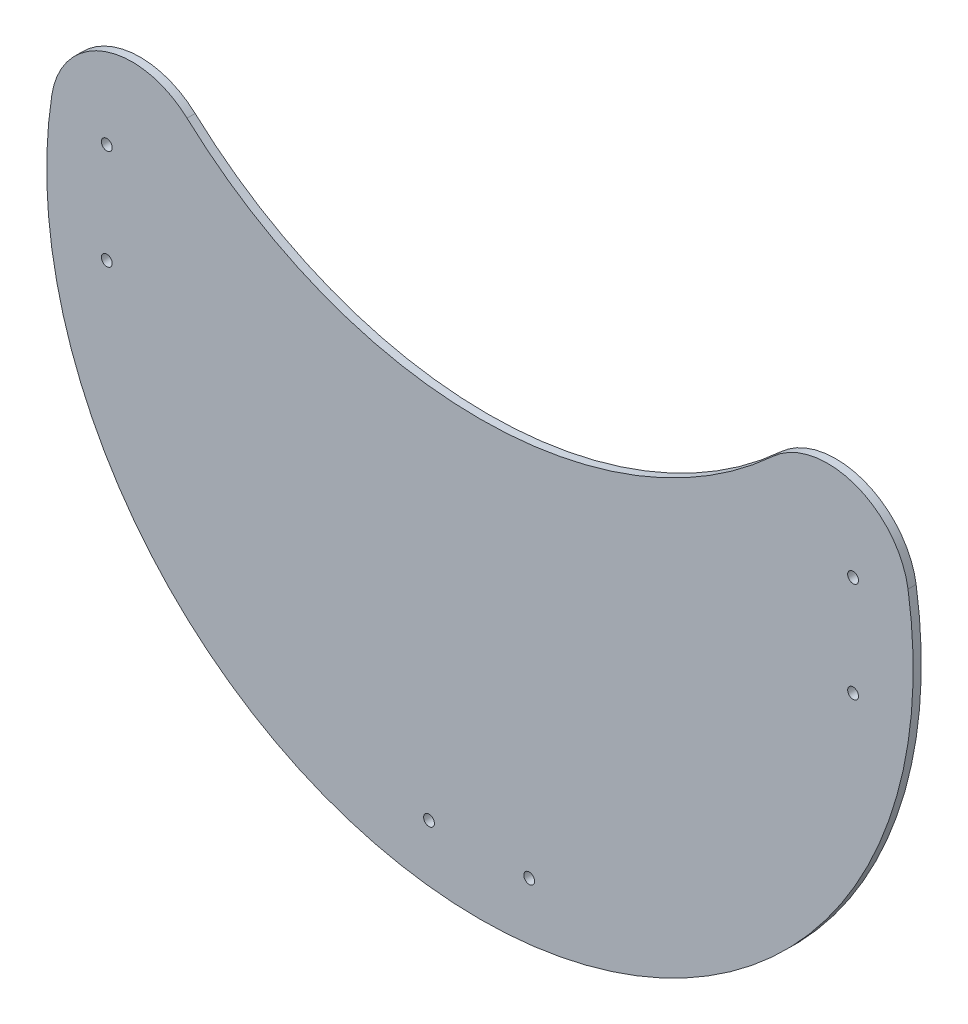
SolidWorks part; units mm, degrees
ref_plane "Front" through (0, 0, 0) normal (0, 0, 1) x (1, 0, 0)
ref_plane "Top" through (0, 0, 0) normal (0, 1, 0) x (1, 0, 0)
ref_plane "Right" through (0, 0, 0) normal (1, 0, 0) x (0, 0, -1)
ref_axis "基准轴1" through (0, -50, 0) along (0, 1, 0)
sketch "草图1" plane through (0, 0, 0) normal (0, 0, 1) x (1, 0, 0)
  circle A6 centre (137.7997, 18.1958) radius 2
  circle A7 centre (137.7997, -18.8042) radius 2
  circle A8 centre (18.1958, -137.7997) radius 2
  circle A9 centre (-18.8042, -137.7997) radius 2
  circle A10 centre (-137.7997, -18.1958) radius 2
  circle A11 centre (-137.7997, 18.8042) radius 2
  arc A36 (-158.0952, 24.6154) -> (158.0952, 24.6154) centre (0, 0) ccw
  arc A37 (-108.1704, 42.1053) -> (108.1704, 42.1053) centre (0, 160) ccw
  arc A38 (-108.1704, 42.1053) -> (-158.0952, 24.6154) centre (-128.4523, 20) ccw
  arc A39 (158.0952, 24.6154) -> (108.1704, 42.1053) centre (128.4523, 20) ccw
  point P22 (0, 0)
  point P45 (0, 0)
  dimension "D1" = 3
  dimension "D2" = 30
  dimension "D3" = 30
extrude "凸台-拉伸1" add sketch "草图1" along normal blind 3
